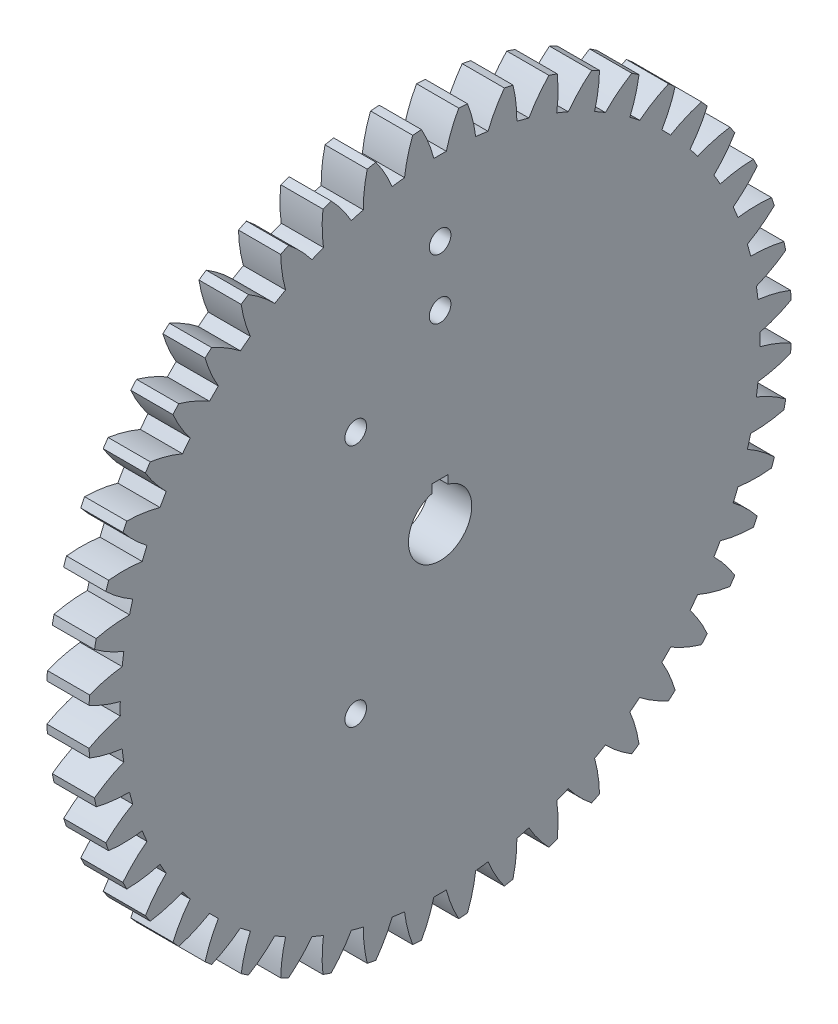
SolidWorks part; units mm, degrees
ref_plane "Plane1" through (0, 0, 0) normal (0, 0, 1) x (1, 0, 0)
ref_plane "Plane2" through (0, 0, 0) normal (0, 1, 0) x (1, 0, 0)
ref_plane "Plane3" through (0, 0, 0) normal (1, 0, 0) x (0, 0, -1)
other "Configuration Table"
sketch "HoldingSke" plane through (0, 0, 0) normal (0, 1, 0) x (1, 0, 0)
  line L0 (0, 0) -> (101.9755, -113.2553)
  line L1 (-15, 0) -> (100, 0) construction
  line L2 (0, 0) -> (-2.1039, 2.3779)
  line L3 (0, 0) -> (-11.863, 4.5341)
  line L4 (0, 0) -> (5.7786, 6.4178)
  line L5 (0, 0) -> (-47.5972, -17.7524)
  line L6 (0, 0) -> (-10.5278, -7.1032)
  line L7 (-2.1039, 2.3779) -> (8.8308, 51.9871)
  line L8 (-76.2, 54.61) -> (-54.9402, 54.61)
  line L9 (-71.009, 38.7566) -> (-53.1078, 45.2721)
  line L10 (-76.2, 71.12) -> (104.1128, 71.12)
  line L11 (0, 0) -> (-12.7, 0)
  line L12 (-76.2, 101.6) -> (-76.0298, 101.6)
  line L13 (24.9733, 27.94) -> (52.9518, 28.4284)
  line L14 (24.9733, 27.94) -> (24.9746, 27.94)
  line L15 (24.9733, 27.94) -> (100.4006, 29.5858)
  circle A0 centre (0, 0) radius 9.525
  circle A1 centre (0, 0) radius 38.1
  circle A2 centre (0, 0) radius 38.1
  circle A3 centre (0, 0) radius 9.525
  dimension "Num_teeth" = 48
  dimension "H" = 19.05
  dimension "Pitch_radius" = 180.3128
  dimension "Width" = 12.7
  dimension "Thickness" = 12.7
sketch "BasProSke" plane through (0, 0, 0) normal (0, 1, 0) x (1, 0, 0)
  line L0 (-10, 0) -> (60, 0) construction
  line L1 (0, 0) -> (0, 105.8333)
  line L2 (0, 0) -> (12.7, 0)
  line L3 (12.7, 0) -> (12.7, 105.8333)
  line L4 (12.7, 105.8333) -> (0, 105.8333)
  dimension "Thickness" = 12.7
  dimension "Diameter" = 211.6667
revolve "Base-Revolve" add sketch "BasProSke" angle 360 about L0
sketch "TooCutSke" plane through (0, 0, 0) normal (1, 0, 0) x (0, 0, -1)
  line L1 (0, 0) -> (0, 107) construction
  line L2 (0, 0) -> (-3.622, 101.5354) construction
  line L3 (0, 0) -> (-13.284, 202.675) construction
  line L4 (-3.622, 101.5354) -> (-6.642, 101.3375) construction
  arc A0 (1.8768, 96.2888) -> (-1.8768, 96.2888) centre (0, 0) ccw
  arc A1 (5.6186, 105.7095) -> (-5.6186, 105.7095) centre (0, 0) ccw
  circle A2 centre (0, 0) radius 101.6 construction
  circle A3 centre (0, 0) radius 95.4728 construction
  arc A4 (-1.8768, 96.2888) -> (-5.6186, 105.7095) centre (-41.2227, 86.1147) ccw
  arc A5 (5.6186, 105.7095) -> (1.8768, 96.2888) centre (41.2227, 86.1147) ccw
extrude "ToothCut" cut sketch "TooCutSke" along normal through all
fillet "Breaks" [suppressed] radius 0.0847 tangent propagation no
fillet "RootFillets" [suppressed] radius 1.0596
pattern_circular "TeethCuts" count 48 every 7.5 about axis through (-10, 0, 0) along (1, 0, 0) of "ToothCut", "RootFillets", "Breaks"
sketch "HubNeaOneSke" plane through (0, 0, 0) normal (-1, 0, 0) x (0, 0, 1)
  circle A0 centre (0, 0) radius 38.1
  dimension "Diameter" = 76.2
extrude "HubNearOne" [suppressed] add sketch "HubNeaOneSke" along normal blind 38.1001
sketch "HubNeaBotSke" plane through (0, 0, 0) normal (-1, 0, 0) x (0, 0, 1)
  circle A0 centre (0, 0) radius 38.1
  dimension "Diameter" = 76.2
extrude "HubNearBoth" [suppressed] add sketch "HubNeaBotSke" along normal blind 19.05
ref_plane "FarPln" through (12.7, 0, 0) normal (1, 0, 0) x (0, 0, -1)
sketch "HubFarSke" plane through (12.7, 0, 0) normal (1, 0, 0) x (0, 0, -1)
  circle A0 centre (0, 0) radius 38.1
  dimension "Diameter" = 76.2
extrude "HubFar" [suppressed] add sketch "HubFarSke" along normal blind 19.05
sketch "BorSke" plane through (0, 0, 0) normal (1, 0, 0) x (0, 0, -1)
  circle A0 centre (0, 0) radius 9.525
  dimension "Diameter" = 19.05
extrude "Bore" cut sketch "BorSke" along normal mid plane 101.6001
sketch "KeySke" plane through (0, 0, 0) normal (1, 0, 0) x (0, 0, -1)
  line L0 (-2.3813, 0) -> (-2.3813, 11.7348)
  line L1 (-2.3813, 11.7348) -> (2.3813, 11.7348)
  line L2 (2.3813, 11.7348) -> (2.3813, 0)
  line L3 (0, 0) -> (0, 34) construction
  line L4 (-2.3813, 0) -> (2.3813, 0)
  dimension "Width" = 4.7625
extrude "Keyway" cut sketch "KeySke" along normal mid plane 101.6001
pattern_circular "Keyway2" [suppressed] count 2 every 90 about axis through (-10, 0, 0) along (1, 0, 0)
sketch "Sketch1" plane through (0, 0, 0) normal (-1, 0, 0) x (0, 0, 1)
  line L0 (-32.7257, 64.77) -> (54.9532, 64.77) construction
  circle A0 centre (0, 73.7743) radius 3.2512
  circle A1 centre (0, 55.7657) radius 3.2512
  point P7 (-12.4968, 58.6999)
  point P8 (-12.4968, 55.9764)
  point P9 (50.5559, 60.1241)
  point P10 (-44.052, 58.7916)
  point P11 (0, 0)
  point P13 (54.9532, 58.3918)
  point P14 (-32.7257, 58.8125)
  dimension "D1" = 6.5024
  dimension "D2" = 18.0086
  dimension "D3" = 64.77
extrude "Cut-Extrude1" cut sketch "Sketch1" against normal through all
sketch "Sketch2" plane through (0, 0, 0) normal (-1, 0, 0) x (0, 0, 1)
  line L0 (41.1124, 0) -> (-29.3128, 0) construction
  circle A0 centre (25.4, -36.703) radius 3.2512
  circle A1 centre (25.4, 36.703) radius 3.2512
  dimension "D2" = 6.5024
  dimension "D1" = 73.406
  dimension "D3" = 25.4
extrude "Cut-Extrude2" cut sketch "Sketch2" against normal through all
equation "' \"Pitch@HoldingSke\" = 4"
equation "' \"Num_teeth@HoldingSke\" = 12"
equation "' \"Ap@HoldingSke\" =  20"
equation "' \"Ap@HoldingSke\" = 20"
equation "' \"Width@HoldingSke\" = 0.5"
equation "' \"Hub_dia@HoldingSke\"= 1"
equation "' \"Hub_dia@HoldingSke\" = 1"
equation "' \"Overall_len@HoldingSke\" = 1.0"
equation "' \"Bore@HoldingSke\" = 0.75"
equation "' \"T_dim@HoldingSke\" = 0.85"
equation "' \"Width@KeySke\" = 0.25"
equation "' \"Show_teeth@HoldingSke\" = 13"
equation "' \"Backlash@HoldingSke\" = 0.009"
equation "' \"Addendum_fac@HoldingSke\" = 1.0"
equation "' \"Dedendum_fac@HoldingSke\" = 1.25"
equation "' \"Dedendum_add@HoldingSke\" = 0.00005"
equation "' \"Clearance_fac@HoldingSke\" = 0.25"
equation "' \"Pitch@HoldingSke\" = 0.5"
equation "' \"Num_teeth@HoldingSke\" = 23"
equation "' \"Show_teeth@HoldingSke\" = 23"
equation "' \"Backlash@HoldingSke\" = 0.0375"
equation "\"Overcut_dia@TooCutSke\" = (\"Num_teeth@HoldingSke\" + 2 * \"Addendum_fac@HoldingSke\") / \"Pitch@HoldingSke\" + 0.002"
equation "\"Pitch_dia@TooCutSke\" = \"Num_teeth@HoldingSke\" / \"Pitch@HoldingSke\""
equation "\"Base_dia@TooCutSke\" = \"Num_teeth@HoldingSke\" / \"Pitch@HoldingSke\" * cos((\"Ap@HoldingSke\"  * 3.14159265 / 180))"
equation "\"Root_dia@TooCutSke\" = (\"Num_teeth@HoldingSke\" + 2) / \"Pitch@HoldingSke\" - 2 * (\"Addendum_fac@HoldingSke\" + \"Dedendum_fac@HoldingSke\") / \"Pitch@HoldingSke\" - \"Dedendum_add@HoldingSke\" * 2"
equation "\"Half_ang@TooCutSke\" = 180 / \"Num_teeth@HoldingSke\""
equation "\"Half_CT@TooCutSke\" = \"Num_teeth@HoldingSke\" / \"Pitch@HoldingSke\" * sin((3.14159265 / 2 / \"Num_teeth@HoldingSke\")) / 2 - 7 * \"Backlash@HoldingSke\" / 4"
equation "\"Flank_rad@TooCutSke\" = \"Num_teeth@HoldingSke\" / \"Pitch@HoldingSke\" / 5"
equation "\"Radius@RootFillets\" = \"Clearance_fac@HoldingSke\" / \"Pitch@HoldingSke\" + \"Dedendum_add@HoldingSke\""
equation "\"Break_rad@Breaks\" = 0.02 / \"Pitch@HoldingSke\""
equation "\"Thickness@HoldingSke\" = \"Width@HoldingSke\""
equation "\"OAL@HoldingSke\" = \"Thickness@HoldingSke\""
equation "\"MHD@HoldingSke\" = (\"Num_teeth@HoldingSke\" + 2) / \"Pitch@HoldingSke\" - 2 * (\"Addendum_fac@HoldingSke\" + \"Dedendum_fac@HoldingSke\")  / \"Pitch@HoldingSke\" - \"Dedendum_add@HoldingSke\" * 2"
equation "\"MBD@HoldingSke\" = (\"Num_teeth@HoldingSke\" + 2) / \"Pitch@HoldingSke\" - 2 * (\"Addendum_fac@HoldingSke\" + \"Dedendum_fac@HoldingSke\")  / \"Pitch@HoldingSke\" - \"Dedendum_add@HoldingSke\" * 2 - 0.002"
equation "\"MHD@HoldingSke\" = ((sgn( \"MHD@HoldingSke\" - \"Hub_dia@HoldingSke\" )-1)*( \"MHD@HoldingSke\" - \"Hub_dia@HoldingSke\" ))/-2+ \"Hub_dia@HoldingSke\""
equation "\"MBD@HoldingSke\" = ((sgn( \"MBD@HoldingSke\" - \"Bore@HoldingSke\" )-1)*( \"MBD@HoldingSke\" - \"Bore@HoldingSke\" ))/-2+ \"Bore@HoldingSke\""
equation "\"OAL@HoldingSke\" = ((sgn( \"OAL@HoldingSke\" - \"Overall_len@HoldingSke\" )+1)*( \"OAL@HoldingSke\" - \"Overall_len@HoldingSke\" ))/2 + \"Overall_len@HoldingSke\" + 0.000002"
equation "\"Num_teeth@TeethCuts\" = int( \"Show_teeth@HoldingSke\" ) + 1"
equation "\"Num_teeth@TeethCuts\" = ((sgn( \"Num_teeth@TeethCuts\" - \"Num_teeth@HoldingSke\" )-1)*( \"Num_teeth@TeethCuts\" - \"Num_teeth@HoldingSke\" ))/-2+ \"Num_teeth@HoldingSke\""
equation "\"Num_teeth@TeethCuts\" = ((sgn( \"Num_teeth@TeethCuts\" - 2.0)+1)*( \"Num_teeth@TeethCuts\" - 2.0))/2 +2.0"
equation "\"Angle@TeethCuts\" = 360.0 / \"Num_teeth@HoldingSke\""
equation "\"Diameter@BasProSke\" = (\"Num_teeth@HoldingSke\" + 2 * \"Addendum_fac@HoldingSke\") / \"Pitch@HoldingSke\""
equation "\"Thickness@BasProSke\"  = \"Thickness@HoldingSke\""
equation "' \"Fillet_rad@BasProSke\" =  \"Thickness@HoldingSke\" * 0.05"
equation "' \"Fillet_rad@BasProSke\" = \"Thickness@HoldingSke\" * 0.05"
equation "\"MHD@HoldingSke\" = ((sgn( \"MHD@HoldingSke\" - \"Root_dia@TooCutSke\" )-1)*( \"MHD@HoldingSke\" - \"Root_dia@TooCutSke\" ))/-2+ \"Root_dia@TooCutSke\""
equation "\"Diameter@HubNeaOneSke\" = \"MHD@HoldingSke\""
equation "\"Length@HubNearOne\" = \"OAL@HoldingSke\" - \"Thickness@BasProSke\""
equation "\"Diameter@HubNeaBotSke\" = \"MHD@HoldingSke\""
equation "\"Length@HubNearBoth\" = ( \"OAL@HoldingSke\" - \"Thickness@BasProSke\" ) / 2.0"
equation "\"Thickness@FarPln\" = \"Thickness@BasProSke\""
equation "\"Diameter@HubFarSke\" = \"MHD@HoldingSke\""
equation "\"Length@HubFar\" = ( \"OAL@HoldingSke\" - \"Thickness@BasProSke\" ) / 2.0"
equation "\"Diameter@BorSke\" = \"MBD@HoldingSke\""
equation "\"D1@Bore\" = \"OAL@HoldingSke\" * 2.0"
equation "\"D1@Keyway\" = \"OAL@HoldingSke\" * 2.0"
equation "\"Offset@KeySke\" = \"T_dim@HoldingSke\" - \"MBD@HoldingSke\" / 2.0"
